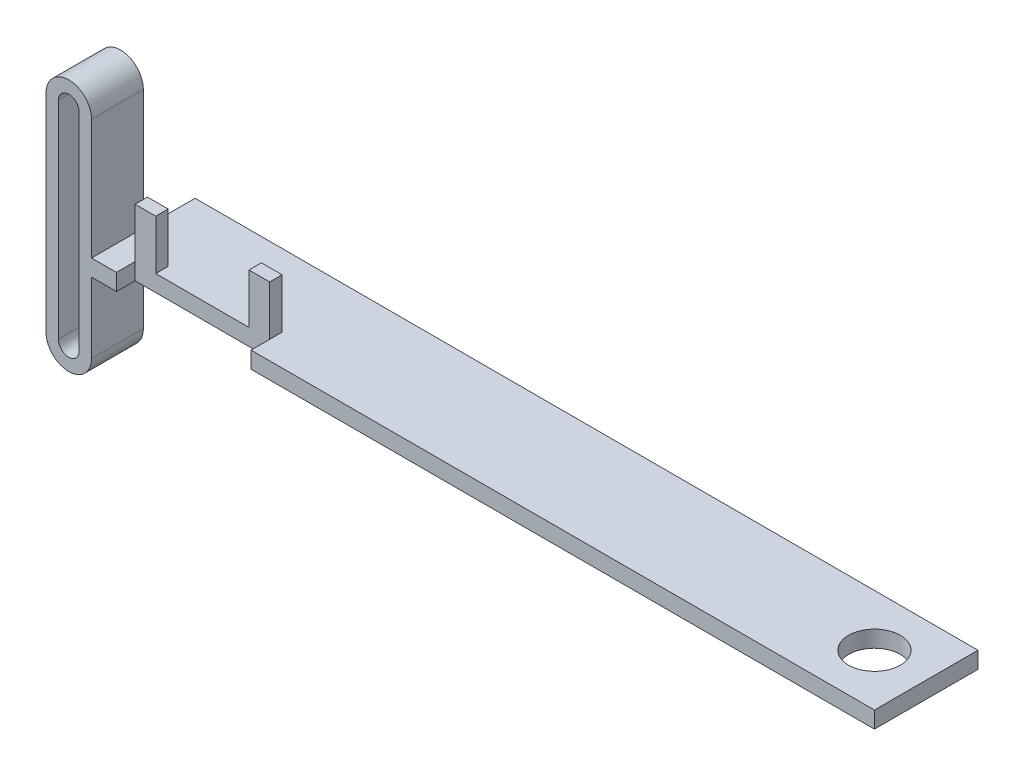
SolidWorks part; units mm, degrees
ref_plane "Front Plane" through (0, 0, 0) normal (0, 0, 1) x (1, 0, 0)
ref_plane "Top Plane" through (0, 0, 0) normal (0, 1, 0) x (1, 0, 0)
ref_plane "Right Plane" through (0, 0, 0) normal (1, 0, 0) x (0, 0, -1)
sketch "Sketch1" plane through (0, 0, 0) normal (0, 1, 0) x (1, 0, 0)
  line L1 (-100, 12.5) -> (100, 12.5)
  line L2 (-100, 12.5) -> (-100, -12.5)
  line L3 (-100, -12.5) -> (100, -12.5)
  line L4 (100, 12.5) -> (100, -12.5)
  line L5 (-100, 12.5) -> (100, -12.5) construction
  line L6 (-100, -12.5) -> (100, 12.5) construction
  circle A4 centre (87.5, 0) radius 6.25
  point P0 (0, 0)
  point P17 (100, 0)
  dimension "D3" = 12.5
  dimension "D4" = 12.5
  dimension "D1" = 25
  dimension "D2" = 200
extrude "Boss-Extrude1" add sketch "Sketch1" along normal blind 4 contours L3 L4 L1 L2 A4 | L3 region at (-2.2016, 0, 0)
sketch "Sketch2" plane through (0, 0, 0) normal (0, 0, 1) x (1, 0, 0)
  line L0 (-94.5, 33) -> (-94.5, -17) construction
  line L1 (-92, 33) -> (-92, -17)
  line L2 (-97, 33) -> (-97, -17)
  line L3 (-89, 33) -> (-89, -17)
  line L4 (-100, 33) -> (-100, -17)
  line L7 (-83, 6.4998) -> (-50.5, 6.4998)
  line L8 (-83, 6.4998) -> (-83, -3.3981)
  line L9 (-83, -3.3981) -> (-50.5, -3.3981)
  line L10 (-50.5, 6.4998) -> (-50.5, -3.3981)
  arc A0 (-92, 33) -> (-97, 33) centre (-94.5, 33) ccw
  arc A1 (-97, -17) -> (-92, -17) centre (-94.5, -17) ccw
  arc A2 (-100, -17) -> (-89, -17) centre (-94.5, -17) ccw
  arc A3 (-89, 33) -> (-100, 33) centre (-94.5, 33) ccw
  point P2 (-94.5, 8)
  point P22 (0, 0)
  dimension "D4" = 5.5
  dimension "D1" = 3
  dimension "D2" = 3
  dimension "D3" = 5
  dimension "D5" = 50
  dimension "D6" = 50
  dimension "D7" = 6
  dimension "D8" = 32.5
extrude "Boss-Extrude2" add sketch "Sketch2" along normal up to surface (12.5 mm away) contours L3 A3 L4 A2 A1 L2 A0 L1 region at (-89.6198, 8, 0) up to face at (0, 2, 12.5)
extrude "Cut-Extrude1" cut sketch "Sketch2<2>" against normal through all both and the other way through all contours L2 A1 L1 A0 region at (-94.5, 8, 0)
sketch "Sketch2<2>" plane through (0, 0, 0) normal (0, 0, 1) x (1, 0, 0) same geometry as "Sketch2"
extrude "Cut-Extrude2" cut sketch "Sketch2<3>" against normal up to surface (12.5 mm away) contours L3 A3 L4 A2 A1 L2 A0 L1 region at (-89.6198, 8, 0) up to face at (4, 2, -12.5)
sketch "Sketch2<3>" plane through (0, 0, 0) normal (0, 0, 1) x (1, 0, 0) same geometry as "Sketch2"
extrude "Cut-Extrude3" cut sketch "Sketch2<5>" along normal up to surface (12.5 mm away) from offset 8 contours L10 L7 L8 L9 region at (-66.75, 1.5509, 0) up to face at (-94.5, 8, 12.5)
sketch "Sketch2<5>" plane through (0, 0, 0) normal (0, 0, 1) x (1, 0, 0) same geometry as "Sketch2"
sketch "Sketch4" plane through (0, 0, 8) normal (0, 0, 1) x (1, 0, 0)
  line L1 (-83, 4) -> (-78, 4)
  line L2 (-83, 4) -> (-83, 16)
  line L3 (-83, 16) -> (-78, 16)
  line L4 (-78, 4) -> (-78, 16)
  line L5 (-50.5, 4) -> (-55.5, 4)
  line L6 (-50.5, 4) -> (-50.5, 16)
  line L7 (-50.5, 16) -> (-55.5, 16)
  line L8 (-55.5, 4) -> (-55.5, 16)
extrude "Boss-Extrude3" add sketch "Sketch4" against normal blind 3
